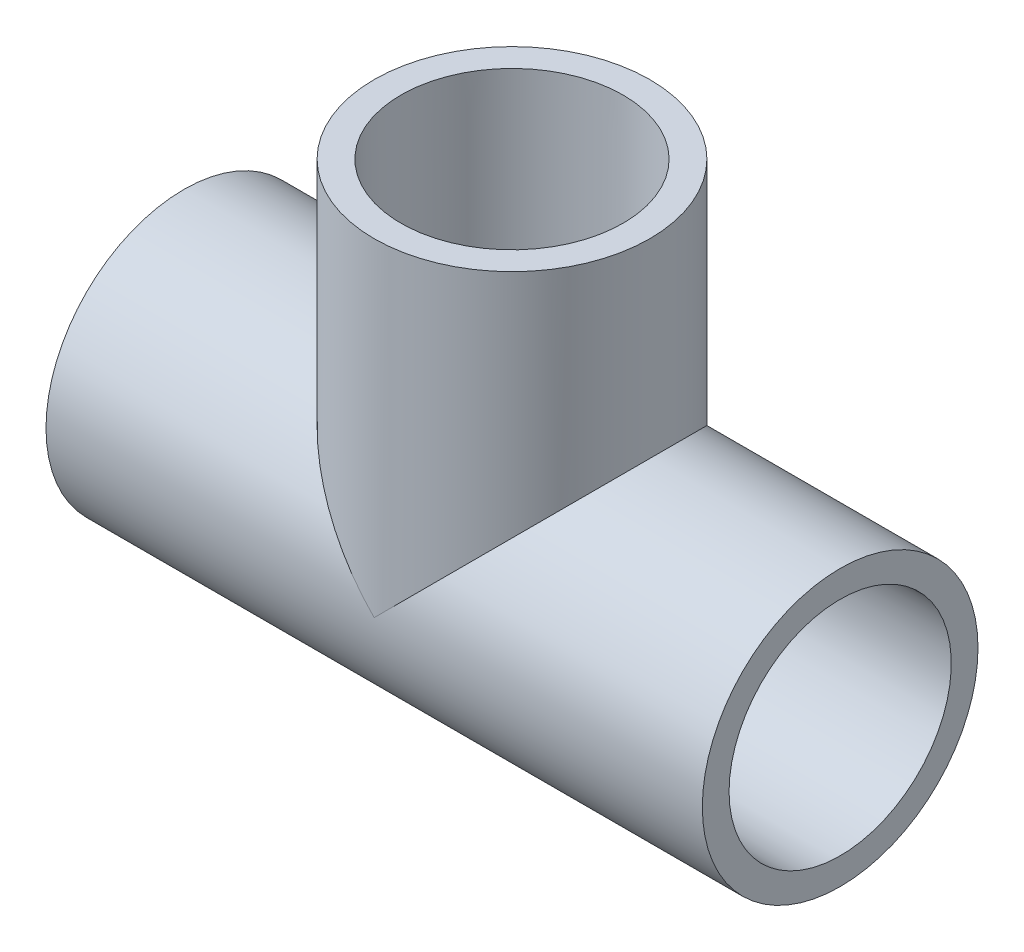
SolidWorks part; units mm, degrees
ref_plane "Front Plane" through (0, 0, 0) normal (0, 0, 1) x (1, 0, 0)
ref_plane "Top Plane" through (0, 0, 0) normal (0, 1, 0) x (1, 0, 0)
ref_plane "Right Plane" through (0, 0, 0) normal (1, 0, 0) x (0, 0, -1)
sketch "Sketch0" plane through (0, 0, 0) normal (0, 0, 1) x (1, 0, 0)
  line L0 (-39.6875, 0) -> (0, 0) construction
  line L1 (0, 0) -> (0, 39.6875) construction
  line L2 (-14.2875, 0) -> (0, 0) construction
  line L3 (0, 0) -> (0, 14.2875) construction
  line L4 (-39.6875, 16.6687) -> (-39.6875, -16.6687) construction
  line L5 (-14.2875, 13.2842) -> (-39.6875, 13.4366) construction
  line L6 (-14.2875, 13.2842) -> (-14.2875, -13.2842) construction
  line L7 (-14.2875, -13.2842) -> (-39.6875, -13.4366) construction
  line L8 (-39.6875, 13.4366) -> (-39.6875, -13.4366) construction
  line L9 (-16.6687, 39.6875) -> (16.6687, 39.6875) construction
  line L10 (-13.4366, 39.6875) -> (13.4366, 39.6875) construction
  line L11 (13.4366, 39.6875) -> (13.2842, 14.2875) construction
  line L12 (13.2842, 14.2875) -> (-13.2842, 14.2875) construction
  line L13 (-13.2842, 14.2875) -> (-13.4366, 39.6875) construction
  line L14 (-14.2875, 10.4648) -> (-14.2875, -10.4648) construction
  line L18 (-10.4648, 14.2875) -> (10.4648, 14.2875) construction
  dimension "H" = 39.6875
  dimension "G" = 14.2875
  dimension "M" = 33.3375
  dimension "OD A" = 26.8732
  dimension "OD B" = 26.5684
  dimension "ID" = 20.9296
sketch "Sketch1" plane through (0, 0, 0) normal (0, 0, 1) x (1, 0, 0)
  line L0 (-39.6875, 0) -> (0, 0) construction
  line L1 (-39.6875, 0) -> (0, 0) construction
  line L3 (-39.6875, -16.6687) -> (-14.2875, -16.6687)
  line L4 (-39.6875, -16.6687) -> (-39.6875, -13.4366)
  line L5 (-39.6875, -13.4366) -> (-14.2875, -13.2842)
  line L6 (-14.2875, -16.6687) -> (-14.2875, -13.2842)
revolve "Revolve1" add sketch "Sketch1" angle 360 about L1
mirror "Mirror1" about plane through (0, 0, 0) normal (1, 0, 0) of bodies 102
sketch "Sketch2" plane through (0, 0, 0) normal (0, 0, 1) x (1, 0, 0)
  line L0 (13.4366, 39.6875) -> (13.2842, 14.2875)
  line L1 (13.2842, 14.2875) -> (16.6687, 14.2875)
  line L2 (16.6687, 14.2875) -> (16.6687, 39.6875)
  line L3 (16.6687, 39.6875) -> (13.4366, 39.6875)
  line L4 (0, 0) -> (0, 39.6875) construction
  line L5 (0, 0) -> (0, 39.6875) construction
revolve "Revolve2" add sketch "Sketch2" angle 360 about L5
sketch "Sketch3" plane through (-14.2875, 0, 0) normal (1, 0, 0) x (0, 0, -1)
  line L0 (-16.6687, 14.2875) -> (16.6687, 14.2875) construction
  line L2 (8.5857, 14.2875) -> (-8.5857, 14.2875)
  circle A1 centre (0, 0) radius 16.6687 construction
  arc A3 (-8.5857, 14.2875) -> (8.5857, 14.2875) centre (0, 0) ccw
extrude "Boss-Extrude1" add sketch "Sketch3" along normal up to surface (28.575 mm away) up to face at (14.2875, 0, 13.2842)
sketch "Sketch4" plane through (0, 14.2875, 0) normal (0, -1, 0) x (1, 0, 0)
  line L0 (14.2875, -8.5857) -> (14.2875, 8.5857)
  line L1 (-14.2875, -8.5857) -> (-14.2875, 8.5857)
  circle A0 centre (0, 0) radius 16.6687 construction
  arc A1 (14.2875, 8.5857) -> (-14.2875, 8.5857) centre (0, 0) ccw
  arc A2 (-14.2875, -8.5857) -> (14.2875, -8.5857) centre (0, 0) ccw
  circle A3 centre (0, 0) radius 16.6687 construction
  circle A4 centre (0, 0) radius 16.6687 construction
extrude "Boss-Extrude2" add sketch "Sketch4" along normal up to surface (14.2875 mm away) up to plane "Top Plane"
sketch "Sketch5" plane through (-14.2875, 0, 0) normal (-1, 0, 0) x (0, 0, 1)
  line L0 (0, 13.2842) -> (0, -13.2842) construction
  circle A0 centre (0, 0) radius 10.4648
extrude "Cut-Extrude1" cut sketch "Sketch5" against normal up to surface (28.575 mm away) up to face at (14.2875, 0, 13.2842)
sketch "Sketch6" plane through (0, 14.2875, 0) normal (0, 1, 0) x (1, 0, 0)
  circle A0 centre (0, 0) radius 10.4648
extrude "Cut-Extrude2" cut sketch "Sketch6" against normal up to vertex (14.2875 mm away) up to point (0, 0, 0)
